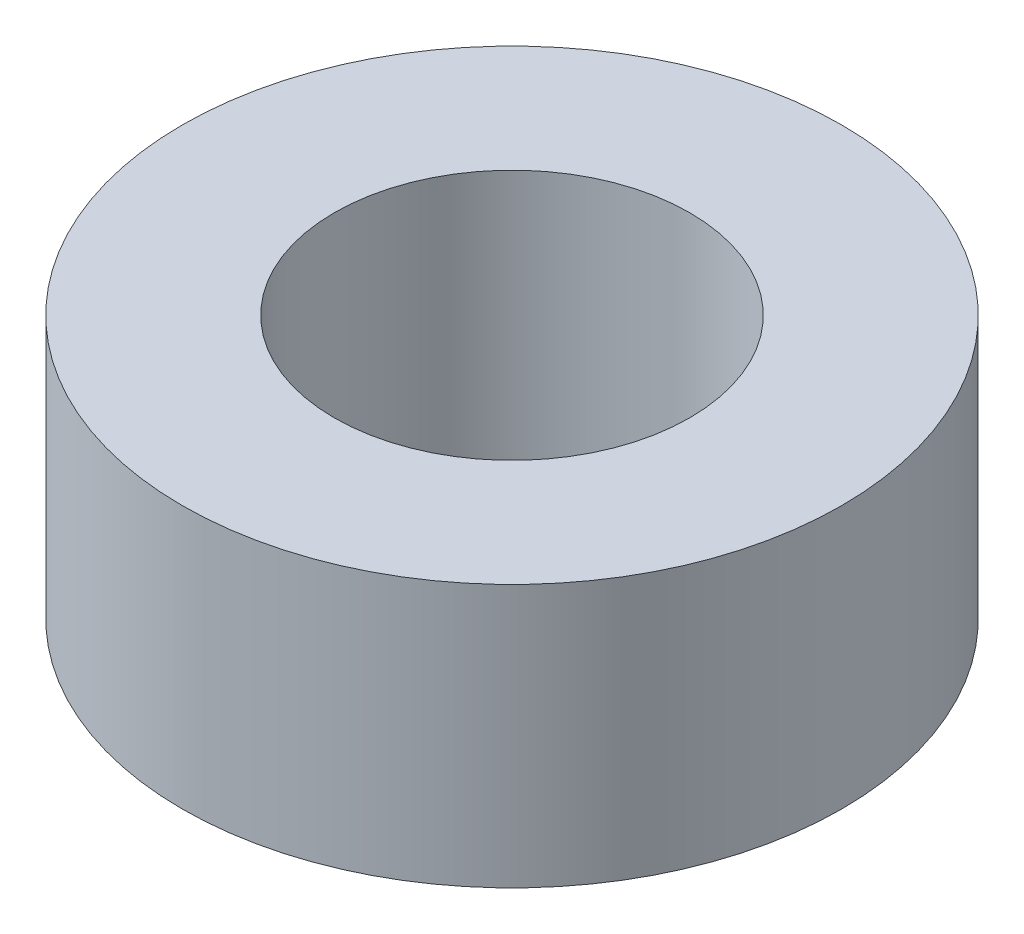
SolidWorks part; units mm, degrees
ref_plane "Front Plane" through (0, 0, 0) normal (0, 0, 1) x (1, 0, 0)
ref_plane "Top Plane" through (0, 0, 0) normal (0, 1, 0) x (1, 0, 0)
ref_plane "Right Plane" through (0, 0, 0) normal (1, 0, 0) x (0, 0, -1)
sketch "Sketch1" plane through (0, 0, 0) normal (0, 1, 0) x (1, 0, 0)
  circle A0 centre (0, 0) radius 20
  dimension "SLEEVE_OD" = 40
extrude "Boss-Extrude1" add sketch "Sketch1" along normal blind 15.9419
sketch "Sketch2" plane through (0, 0, 0) normal (0, 1, 0) x (1, 0, 0)
  circle A0 centre (0, 0) radius 10.7799
  dimension "BORE_D" = 21.5598
extrude "Cut-Extrude1" cut sketch "Sketch2" along normal through all
chamfer "Chamfer1" distance 3.9049 angle 60 rebuild error yes
